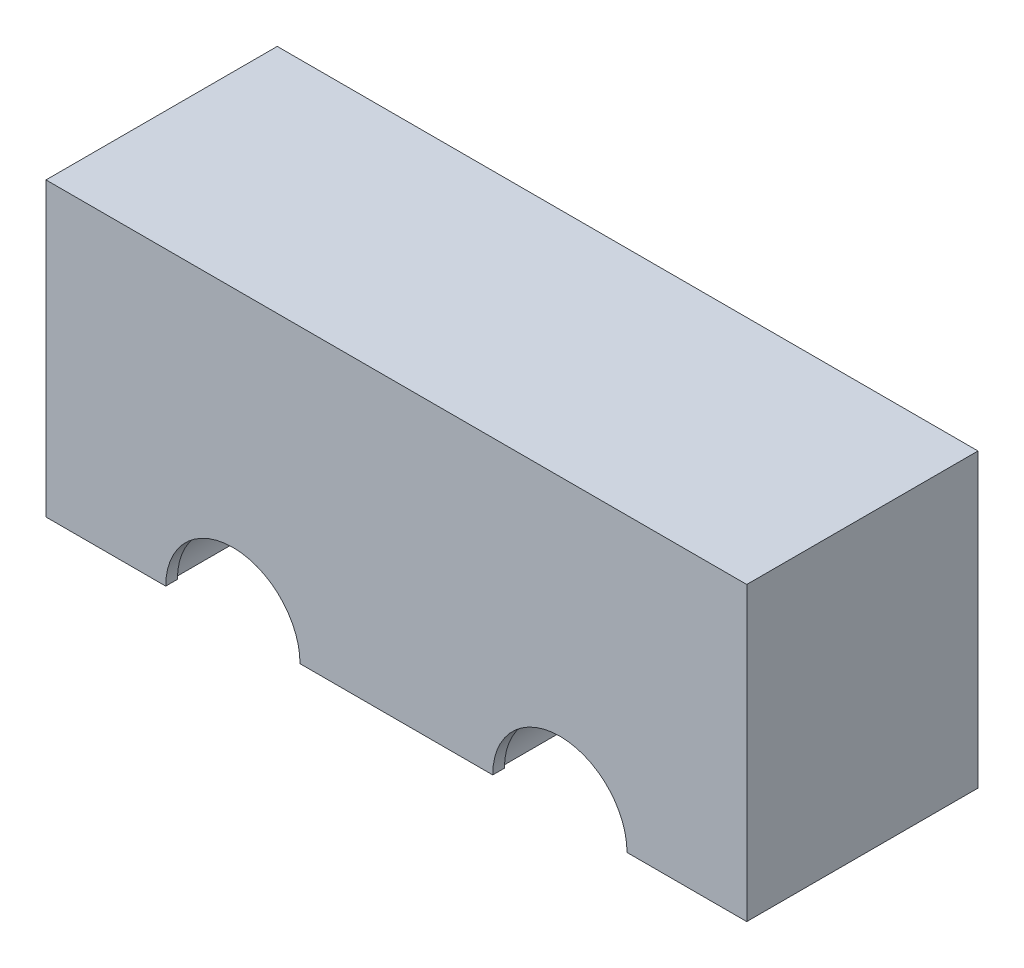
SolidWorks part; units mm, degrees
ref_plane "Front Plane" through (0, 0, 0) normal (0, 0, 1) x (1, 0, 0)
ref_plane "Top Plane" through (0, 0, 0) normal (0, 1, 0) x (1, 0, 0)
ref_plane "Right Plane" through (0, 0, 0) normal (1, 0, 0) x (0, 0, -1)
sketch "Sketch1" plane through (0, 0, 0) normal (0, 0, 1) x (1, 0, 0)
  line L1 (-30, 0) -> (30, 0)
  line L2 (-30, 0) -> (-30, 25)
  line L3 (-30, 25) -> (30, 25)
  line L4 (30, 0) -> (30, 25)
  point P5 (0, 0)
  dimension "D1" = 25
  dimension "D2" = 60
extrude "Boss-Extrude1" add sketch "Sketch1" along normal blind 19.8
sketch "Sketch2" plane through (0, 0, 0) normal (0, 0, -1) x (-1, 0, 0)
  line L0 (30, 0) -> (-30, 0) construction
  line L1 (-20, 0) -> (-8, 0)
  line L2 (8, 0) -> (20, 0)
  arc A0 (-20, 0) -> (-8, 0) centre (-14, 0) cw
  arc A1 (20, 0) -> (8, 0) centre (14, 0) ccw
  dimension "D1" = 6
  dimension "D3" = 6
  dimension "D2" = 10
  dimension "D4" = 10
extrude "Cut-Extrude3" cut sketch "Sketch2" against normal up to surface (19.8 mm away) up to face at (0, 12.5, 19.8)
sketch "Sketch4" plane through (0, 0, 0) normal (0, 0, -1) x (-1, 0, 0)
  line L0 (-19.75, 0) -> (-20, 0)
  line L1 (-8.25, 0) -> (-8, 0)
  line L2 (8, 0) -> (8.25, 0)
  line L3 (20, 0) -> (19.75, 0)
  line L4 (8, 0) -> (-8, 0) construction
  arc A0 (-20, 0) -> (-8, 0) centre (-14, 0) cw
  arc A1 (-19.75, 0) -> (-8.25, 0) centre (-14, 0) cw
  arc A2 (8, 0) -> (20, 0) centre (14, 0) cw
  arc A3 (8.25, 0) -> (19.75, 0) centre (14, 0) cw
  dimension "D1" = 5.75
extrude "Boss-Extrude2" add sketch "Sketch4" against normal blind 1
extrude "Boss-Extrude3" add sketch "Sketch4<2>" against normal blind 1 from offset 18.8 offset against normal yes
sketch "Sketch4<2>" plane through (0, 0, 0) normal (0, 0, -1) x (-1, 0, 0) same geometry as "Sketch4"
